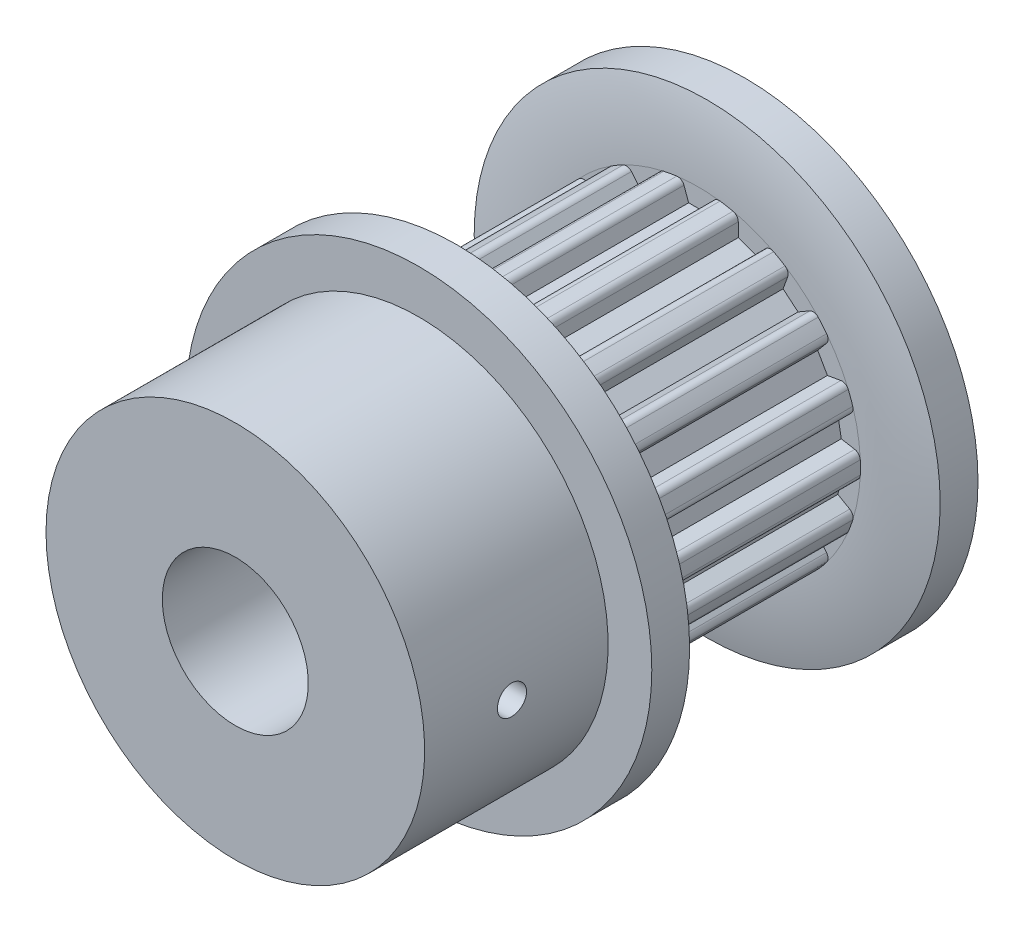
SolidWorks part; units mm, degrees
ref_plane "Front Plane" through (0, 0, 0) normal (0, 0, 1) x (1, 0, 0)
ref_plane "Top Plane" through (0, 0, 0) normal (0, 1, 0) x (1, 0, 0)
ref_plane "Right Plane" through (0, 0, 0) normal (1, 0, 0) x (0, 0, -1)
sketch "Sketch8" plane through (0, 0, 0) normal (1, 0, 0) x (0, 0, -1)
  line L0 (7.5979, 0) -> (-14.162, 0) construction
  line L1 (5.6, -2.5063) -> (5.6, -8)
  line L2 (4, -5.5625) -> (-4, -5.5625)
  line L4 (5.6, -8) -> (4.3016, -8)
  line L6 (-4.3016, -8) -> (-5.6, -8)
  line L8 (-5.6, -8) -> (-5.6, -6.5)
  line L10 (-5.6, -6.5) -> (-11.9, -6.5)
  line L12 (-11.9, -6.5) -> (-11.9, -2.5063)
  line L13 (5.6, -2.5063) -> (-11.9, -2.5063)
  arc A0 (4.3016, -8) -> (4, -5.5625) centre (14, -5.5625) cw
  arc A2 (-4.3016, -8) -> (-4, -5.5625) centre (-14, -5.5625) ccw
  dimension "D1" = 2.5063
revolve "Revolve1" add sketch "Sketch8" angle 360 about L0
sketch "Sketch7" plane through (0, 0, 0) normal (0, 0, 1) x (1, 0, 0)
  line L0 (-1.9984, 4.5111) -> (-1.3688, 4.7402)
  line L4 (-1.3688, 4.7402) -> (-1.3688, 5.2095)
  line L5 (-1.9984, 4.5111) -> (-2.3, 4.8705)
  line L7 (-0.335, 4.9225) -> (0.335, 4.9225)
  line L9 (0.335, 4.9225) -> (0.4955, 5.3635)
  line L11 (-0.335, 4.9225) -> (-0.4955, 5.3635)
  line L12 (1.3688, 4.7402) -> (1.9984, 4.5111)
  line L13 (1.9984, 4.5111) -> (2.3, 4.8705)
  line L14 (1.3688, 4.7402) -> (1.3688, 5.2095)
  line L15 (2.9075, 3.9862) -> (3.4207, 3.5555)
  line L16 (3.4207, 3.5555) -> (3.8271, 3.7902)
  line L17 (2.9075, 3.9862) -> (3.068, 4.4272)
  line L18 (4.0955, 2.7514) -> (4.4305, 2.1711)
  line L19 (4.4305, 2.1711) -> (4.8926, 2.2526)
  line L20 (4.0955, 2.7514) -> (4.3971, 3.1108)
  line L21 (4.7895, 1.1847) -> (4.9059, 0.5249)
  line L22 (4.9059, 0.5249) -> (5.368, 0.4434)
  line L23 (4.7895, 1.1847) -> (5.1959, 1.4193)
  line L24 (4.9059, -0.5249) -> (4.7895, -1.1847)
  line L25 (4.7895, -1.1847) -> (5.1959, -1.4193)
  line L26 (4.9059, -0.5249) -> (5.368, -0.4434)
  line L27 (4.4305, -2.1711) -> (4.0955, -2.7514)
  line L28 (4.0955, -2.7514) -> (4.3971, -3.1108)
  line L29 (4.4305, -2.1711) -> (4.8926, -2.2526)
  line L30 (3.4207, -3.5555) -> (2.9075, -3.9862)
  line L31 (2.9075, -3.9862) -> (3.068, -4.4272)
  line L32 (3.4207, -3.5555) -> (3.8271, -3.7902)
  line L33 (1.9984, -4.5111) -> (1.3688, -4.7402)
  line L34 (1.3688, -4.7402) -> (1.3688, -5.2095)
  line L35 (1.9984, -4.5111) -> (2.3, -4.8705)
  line L36 (0.335, -4.9225) -> (-0.335, -4.9225)
  line L37 (-0.335, -4.9225) -> (-0.4955, -5.3635)
  line L38 (0.335, -4.9225) -> (0.4955, -5.3635)
  line L39 (-1.3688, -4.7402) -> (-1.9984, -4.5111)
  line L40 (-1.9984, -4.5111) -> (-2.3, -4.8705)
  line L41 (-1.3688, -4.7402) -> (-1.3688, -5.2095)
  line L42 (-2.9075, -3.9862) -> (-3.4207, -3.5555)
  line L43 (-3.4207, -3.5555) -> (-3.8271, -3.7902)
  line L44 (-2.9075, -3.9862) -> (-3.068, -4.4272)
  line L45 (-4.0955, -2.7514) -> (-4.4305, -2.1711)
  line L46 (-4.4305, -2.1711) -> (-4.8926, -2.2526)
  line L47 (-4.0955, -2.7514) -> (-4.3971, -3.1108)
  line L48 (-4.7895, -1.1847) -> (-4.9059, -0.5249)
  line L49 (-4.9059, -0.5249) -> (-5.368, -0.4434)
  line L50 (-4.7895, -1.1847) -> (-5.1959, -1.4193)
  line L51 (-4.9059, 0.5249) -> (-4.7895, 1.1847)
  line L52 (-4.7895, 1.1847) -> (-5.1959, 1.4193)
  line L53 (-4.9059, 0.5249) -> (-5.368, 0.4434)
  line L54 (-4.4305, 2.1711) -> (-4.0955, 2.7514)
  line L55 (-4.0955, 2.7514) -> (-4.3971, 3.1108)
  line L56 (-4.4305, 2.1711) -> (-4.8926, 2.2526)
  line L57 (-3.4207, 3.5555) -> (-2.9075, 3.9862)
  line L58 (-2.9075, 3.9862) -> (-3.068, 4.4272)
  line L59 (-3.4207, 3.5555) -> (-3.8271, 3.7902)
  arc A0 (0.7423, 5.5127) -> (0.4955, 5.3635) centre (0.7116, 5.2848) ccw
  arc A2 (-1.1879, 5.4342) -> (-1.3688, 5.2095) centre (-1.1388, 5.2095) ccw
  arc A3 (-2.3, 4.8705) -> (-2.583, 4.9264) centre (-2.4762, 4.7227) ccw
  arc A4 (-0.4955, 5.3635) -> (-0.7423, 5.5127) centre (-0.7116, 5.2848) ccw
  arc A6 (0.7423, 5.5127) -> (-0.7423, 5.5127) centre (0, 0) ccw
  arc A7 (2.583, 4.9264) -> (2.3, 4.8705) centre (2.4762, 4.7227) ccw
  arc A8 (-1.1879, 5.4342) -> (-2.583, 4.9264) centre (0, 0) ccw
  arc A9 (1.3688, 5.2095) -> (1.1879, 5.4342) centre (1.1388, 5.2095) ccw
  arc A10 (2.583, 4.9264) -> (1.1879, 5.4342) centre (0, 0) ccw
  arc A11 (4.1122, 3.7459) -> (3.8271, 3.7902) centre (3.9421, 3.591) ccw
  arc A12 (3.068, 4.4272) -> (2.9749, 4.7002) centre (2.8519, 4.5058) ccw
  arc A13 (4.1122, 3.7459) -> (2.9749, 4.7002) centre (0, 0) ccw
  arc A14 (5.1453, 2.1135) -> (4.8926, 2.2526) centre (4.9326, 2.0261) ccw
  arc A15 (4.3971, 3.1108) -> (4.403, 3.3992) centre (4.221, 3.2587) ccw
  arc A16 (5.1453, 2.1135) -> (4.403, 3.3992) centre (0, 0) ccw
  arc A17 (5.5579, 0.2262) -> (5.368, 0.4434) centre (5.3281, 0.2169) ccw
  arc A18 (5.1959, 1.4193) -> (5.3001, 1.6883) centre (5.0809, 1.6185) ccw
  arc A19 (5.5579, 0.2262) -> (5.3001, 1.6883) centre (0, 0) ccw
  arc A20 (5.3001, -1.6883) -> (5.1959, -1.4193) centre (5.0809, -1.6185) ccw
  arc A21 (5.368, -0.4434) -> (5.5579, -0.2262) centre (5.3281, -0.2169) ccw
  arc A22 (5.3001, -1.6883) -> (5.5579, -0.2262) centre (0, 0) ccw
  arc A23 (4.403, -3.3992) -> (4.3971, -3.1108) centre (4.221, -3.2587) ccw
  arc A24 (4.8926, -2.2526) -> (5.1453, -2.1135) centre (4.9326, -2.0261) ccw
  arc A25 (4.403, -3.3992) -> (5.1453, -2.1135) centre (0, 0) ccw
  arc A26 (2.9749, -4.7002) -> (3.068, -4.4272) centre (2.8519, -4.5058) ccw
  arc A27 (3.8271, -3.7902) -> (4.1122, -3.7459) centre (3.9421, -3.591) ccw
  arc A28 (2.9749, -4.7002) -> (4.1122, -3.7459) centre (0, 0) ccw
  arc A29 (1.1879, -5.4342) -> (1.3688, -5.2095) centre (1.1388, -5.2095) ccw
  arc A30 (2.3, -4.8705) -> (2.583, -4.9264) centre (2.4762, -4.7227) ccw
  arc A31 (1.1879, -5.4342) -> (2.583, -4.9264) centre (0, 0) ccw
  arc A32 (-0.7423, -5.5127) -> (-0.4955, -5.3635) centre (-0.7116, -5.2848) ccw
  arc A33 (0.4955, -5.3635) -> (0.7423, -5.5127) centre (0.7116, -5.2848) ccw
  arc A34 (-0.7423, -5.5127) -> (0.7423, -5.5127) centre (0, 0) ccw
  arc A35 (-2.583, -4.9264) -> (-2.3, -4.8705) centre (-2.4762, -4.7227) ccw
  arc A36 (-1.3688, -5.2095) -> (-1.1879, -5.4342) centre (-1.1388, -5.2095) ccw
  arc A37 (-2.583, -4.9264) -> (-1.1879, -5.4342) centre (0, 0) ccw
  arc A38 (-4.1122, -3.7459) -> (-3.8271, -3.7902) centre (-3.9421, -3.591) ccw
  arc A39 (-3.068, -4.4272) -> (-2.9749, -4.7002) centre (-2.8519, -4.5058) ccw
  arc A40 (-4.1122, -3.7459) -> (-2.9749, -4.7002) centre (0, 0) ccw
  arc A41 (-5.1453, -2.1135) -> (-4.8926, -2.2526) centre (-4.9326, -2.0261) ccw
  arc A42 (-4.3971, -3.1108) -> (-4.403, -3.3992) centre (-4.221, -3.2587) ccw
  arc A43 (-5.1453, -2.1135) -> (-4.403, -3.3992) centre (0, 0) ccw
  arc A44 (-5.5579, -0.2262) -> (-5.368, -0.4434) centre (-5.3281, -0.2169) ccw
  arc A45 (-5.1959, -1.4193) -> (-5.3001, -1.6883) centre (-5.0809, -1.6185) ccw
  arc A46 (-5.5579, -0.2262) -> (-5.3001, -1.6883) centre (0, 0) ccw
  arc A47 (-5.3001, 1.6883) -> (-5.1959, 1.4193) centre (-5.0809, 1.6185) ccw
  arc A48 (-5.368, 0.4434) -> (-5.5579, 0.2262) centre (-5.3281, 0.2169) ccw
  arc A49 (-5.3001, 1.6883) -> (-5.5579, 0.2262) centre (0, 0) ccw
  arc A50 (-4.403, 3.3992) -> (-4.3971, 3.1108) centre (-4.221, 3.2587) ccw
  arc A51 (-4.8926, 2.2526) -> (-5.1453, 2.1135) centre (-4.9326, 2.0261) ccw
  arc A52 (-4.403, 3.3992) -> (-5.1453, 2.1135) centre (0, 0) ccw
  arc A53 (-2.9749, 4.7002) -> (-3.068, 4.4272) centre (-2.8519, 4.5058) ccw
  arc A54 (-3.8271, 3.7902) -> (-4.1122, 3.7459) centre (-3.9421, 3.591) ccw
  arc A55 (-2.9749, 4.7002) -> (-4.1122, 3.7459) centre (0, 0) ccw
  point P152 (0, 0)
  dimension "D1" = 18
extrude "Cut-Extrude1" cut sketch "Sketch7" against normal blind 4 and the other way blind 4
hole_wizard "Ø1.0 (1) Diameter Hole1" positions "3DSketch1" profile "Sketch6" hole size "Ø1.0" standard "ANSI Metric" end condition up to next
sketch3d "3DSketch1"
  point P0 (6.5, 0, 8.9)
sketch "Sketch6" plane through (6.5, 0, 8.9) normal (0, 1, 0) x (0, 0, -1)
  line L0 (0, 0) -> (0, 3.9937)
  line L1 (0, 3.9937) -> (0.5, 3.9937)
  line L2 (0.5, 3.9937) -> (0.5, 0)
  line L5 (0.5, 0) -> (0, 0)
  line L11 (0, -6.35) -> (0, 107.95) construction
  dimension "Thru Hole Dia." = 1
  dimension "Thru Hole Depth" = 3.9937
